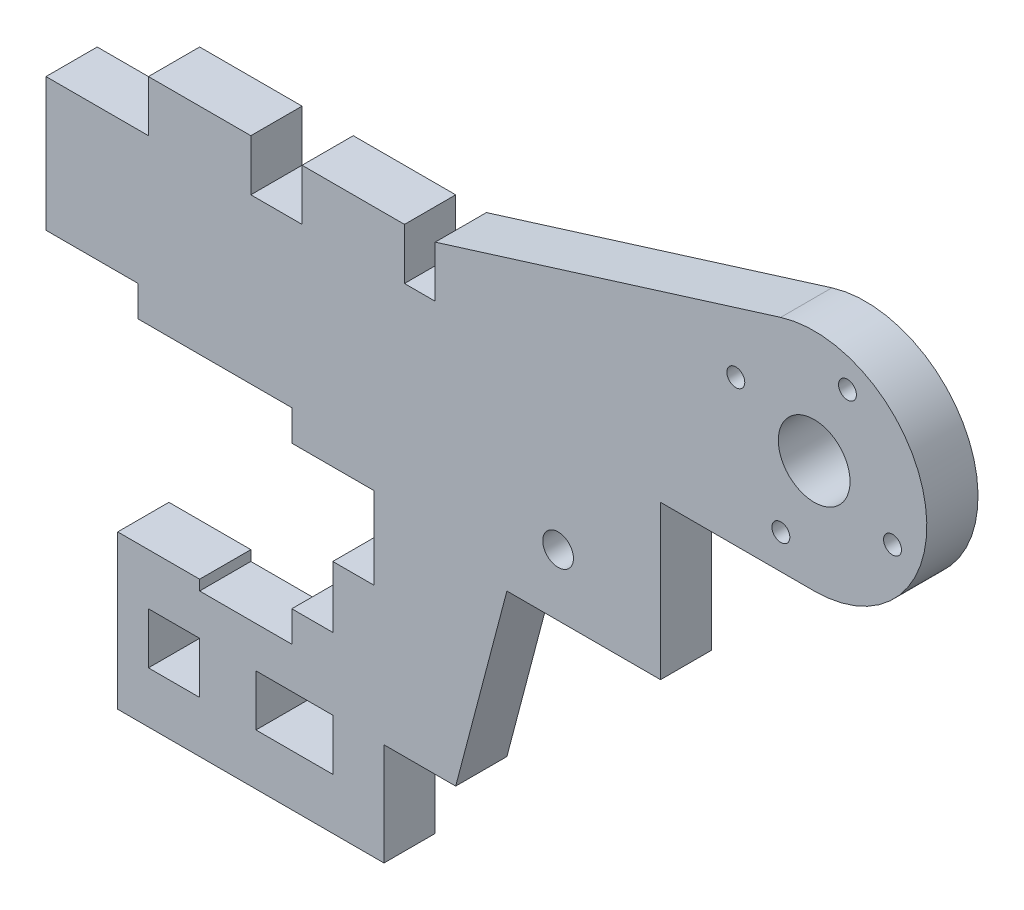
SolidWorks part; units mm, degrees
ref_plane "Plan de face" through (0, 0, 0) normal (0, 0, 1) x (1, 0, 0)
ref_plane "Plan de dessus" through (0, 0, 0) normal (0, 1, 0) x (1, 0, 0)
ref_plane "Plan de droite" through (0, 0, 0) normal (1, 0, 0) x (0, 0, -1)
sketch "Esquisse1" plane through (0, 0, 0) normal (0, 0, 1) x (1, 0, 0)
  line L0 (-8, -10) -> (18, -10)
  line L1 (18, 0) -> (18, -10)
  line L2 (0, 5) -> (0, 4)
  line L3 (5, 40) -> (10, 40)
  line L4 (56.75, 37.35) -> (63.25, 52.65) construction
  line L5 (20, 40) -> (23, 40)
  line L6 (-5, 40) -> (-5, 45)
  line L7 (-5, 45) -> (5, 45)
  line L8 (5, 40) -> (5, 45)
  line L9 (18, 0) -> (25, 0)
  line L10 (10, 40) -> (10, 45)
  line L11 (10, 45) -> (20, 45)
  line L12 (20, 40) -> (20, 45)
  line L13 (60, 34) -> (45, 34)
  line L14 (13, 0) -> (5.5, 0)
  line L15 (13, 0) -> (13, -5)
  line L16 (13, -5) -> (5.5, -5)
  line L17 (5.5, 0) -> (5.5, -5)
  line L18 (0, 0) -> (-5, 0)
  line L19 (-6, 27) -> (-6, 24)
  line L20 (0, 4) -> (9, 4)
  line L21 (60, 45) -> (52.35, 45) construction
  line L22 (-6, 24) -> (9, 24)
  line L23 (17, 13) -> (17, 21)
  line L24 (0, 0) -> (0, -5)
  line L25 (0, 0) -> (0, 5)
  line L26 (0, 5) -> (-8, 5)
  line L27 (-8, -10) -> (-8, 5)
  line L28 (-5, 40) -> (-15, 40)
  line L29 (0, -5) -> (-5, -5)
  line L30 (-6, 27) -> (-15, 27)
  line L31 (-15, 40) -> (-15, 27)
  line L32 (17, 21) -> (9, 21)
  line L33 (52.35, 45) -> (52.35, 48.25) construction
  line L34 (9, 7) -> (13, 7)
  line L35 (9, 21) -> (9, 24)
  line L36 (17, 13) -> (13, 13)
  line L37 (67.65, 41.75) -> (52.35, 48.25) construction
  line L38 (30, 19) -> (25, 0)
  line L39 (9, 7) -> (9, 4)
  line L40 (-5, 0) -> (-5, -5)
  line L41 (13, 7) -> (13, 13)
  line L42 (56.7297, 55.5026) -> (23, 45)
  line L43 (45, 19) -> (45, 34)
  line L46 (23, 40) -> (23, 45)
  line L48 (45, 19) -> (30, 19)
  circle A0 centre (35, 25) radius 1.5
  circle A1 centre (60, 45) radius 3.5
  arc A2 (60, 34) -> (56.7297, 55.5026) centre (60, 45) ccw
  circle A3 centre (52.35, 45) radius 0.875 construction
  circle A4 centre (52.35, 48.25) radius 0.875
  circle A5 centre (63.25, 52.65) radius 0.875
  circle A6 centre (67.65, 41.75) radius 0.875
  circle A7 centre (56.75, 37.35) radius 0.875
  point P56 (60, 45)
  dimension "D18" = 7
  dimension "D19" = 3
  dimension "D25" = 3.25
  dimension "D27" = 11
  dimension "D28" = 1.75
  dimension "D24" = 7
  dimension "D3" = 10
  dimension "D4" = 5
  dimension "D5" = 5
  dimension "D6" = 8
  dimension "D7" = 15
  dimension "D8" = 10
  dimension "D9" = 16
  dimension "D10" = 3
  dimension "D11" = 9
  dimension "D12" = 4
  dimension "D13" = 10
  dimension "D14" = 3
  dimension "D15" = 8
  dimension "D16" = 8
  dimension "D17" = 8
  dimension "D20" = 20
  dimension "D21" = 5
  dimension "D22" = 17
  dimension "D23" = 25
  dimension "D26" = 7.65
  dimension "D30" = 4
  dimension "D31" = 3
  dimension "D32" = 1
  dimension "D33" = 15
  dimension "D34" = 40
  dimension "D35" = 26
  dimension "D36" = 5
  dimension "D37" = 5
  dimension "D38" = 7.5
  dimension "D39" = 5
  dimension "D40" = 104.744
  dimension "D41" = 3
  dimension "D42" = 6
  dimension "D43" = 15
  dimension "D29" = 4
extrude "Boss.-Extru.1" add sketch "Esquisse1" along normal blind 5 contours L5 L12 L11 L10 L3 L8 L7 L6 | L28 L31 L30 | L19 L22 L23 L20 L2 L25 L9 | L27 L25 L26 region at (24.5886, 28.2926, 0)
